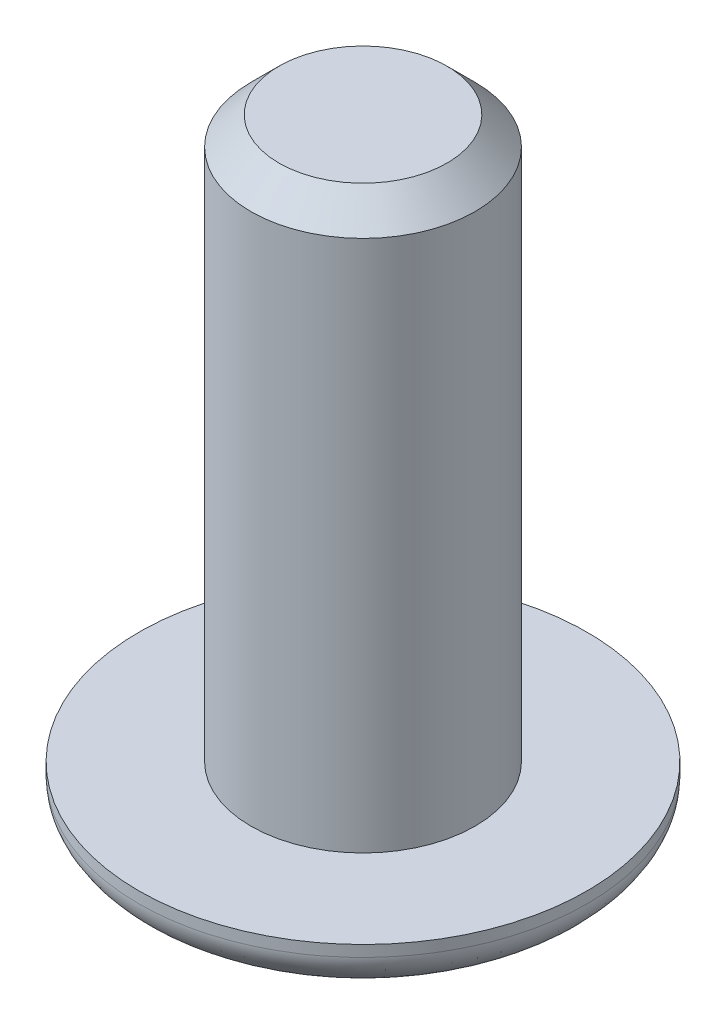
SolidWorks part; units mm, degrees
ref_plane "前视基准面" through (0, 0, 0) normal (0, 0, 1) x (1, 0, 0)
ref_plane "上视基准面" through (0, 0, 0) normal (0, 1, 0) x (1, 0, 0)
ref_plane "右视基准面" through (0, 0, 0) normal (1, 0, 0) x (0, 0, -1)
sketch "草图1" plane through (0, 0, 0) normal (0, 1, 0) x (1, 0, 0)
  line L1 (1.4434, 0) -> (0.7217, 1.25)
  line L2 (0.7217, 1.25) -> (-0.7217, 1.25)
  line L3 (-0.7217, 1.25) -> (-1.4434, 0)
  line L4 (-1.4434, 0) -> (-0.7217, -1.25)
  line L5 (-0.7217, -1.25) -> (0.7217, -1.25)
  line L6 (0.7217, -1.25) -> (1.4434, 0)
  circle A0 centre (0, 0) radius 4
  circle A1 centre (0, 0) radius 1.25 construction
extrude "凸台-拉伸1" add sketch "草图1" along normal blind 1.2
sketch "草图2" plane through (0, 1.2, 0) normal (0, 1, 0) x (1, 0, 0)
  circle A0 centre (0, 0) radius 2
extrude "凸台-拉伸2" add sketch "草图2" along normal blind 10
chamfer "倒角1" distance 0.5 angle 45 1 edges at (0, 11.2, 2)
fillet "圆角1" radius 2 1 edges at (0, 0, 4) second distance 1 first distance on face at (0, 0, 4)
